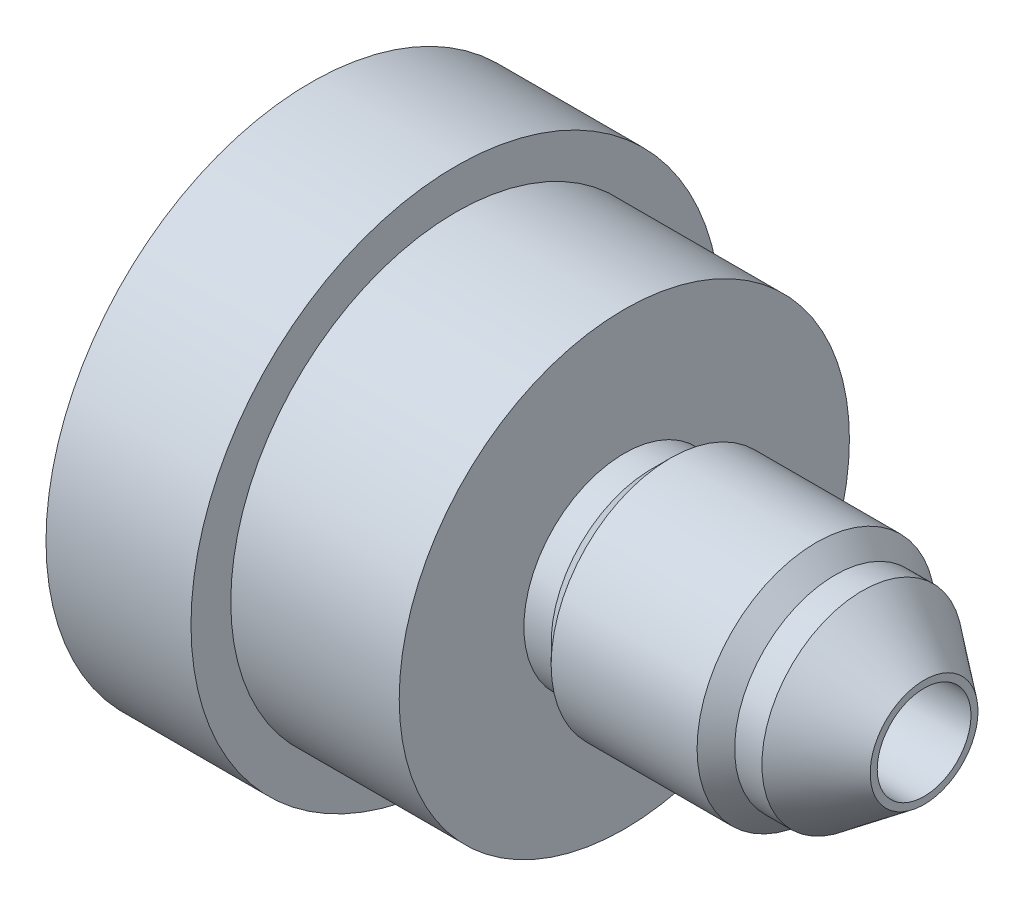
SolidWorks part; units mm, degrees
ref_plane "Front Plane" through (0, 0, 0) normal (0, 0, 1) x (1, 0, 0)
ref_plane "Top Plane" through (0, 0, 0) normal (0, 1, 0) x (1, 0, 0)
ref_plane "Right Plane" through (0, 0, 0) normal (1, 0, 0) x (0, 0, -1)
sketch "Sketch1" plane through (0, 0, 0) normal (0, 0, 1) x (1, 0, 0)
  line L0 (-14.2875, 0) -> (14.2875, 0) construction
  line L1 (-14.2875, 12.3444) -> (-14.2875, 11.176)
  line L2 (-14.2875, 11.176) -> (-2.3552, 2.1844)
  line L3 (-2.3552, 2.1844) -> (14.2875, 2.1844)
  line L4 (14.2875, 2.1844) -> (14.2875, 2.5121)
  line L5 (14.2875, 2.5121) -> (10.2477, 5.5562) construction
  line L6 (10.2477, 5.5562) -> (0.3175, 5.5562)
  line L7 (0.3175, 10.4902) -> (0.3175, 5.5562)
  line L8 (0.3175, 10.4902) -> (-7.5311, 10.4902)
  line L9 (-14.2875, 12.3444) -> (-7.5311, 12.3444)
  line L10 (-7.5311, 12.3444) -> (-7.5311, 10.4902)
  line L11 (10.2477, 5.5562) -> (14.2875, 5.5562)
  line L12 (14.2875, 5.5562) -> (14.2875, 2.5121)
  dimension "A" = 28.575
  dimension "OD" = 11.1125
  dimension "Min" = 4.3688
  dimension "D3" = 5.0241
  dimension "D4" = 37
  dimension "B" = 6.7564
  dimension "G" = 24.6888
  dimension "C" = 13.97
  dimension "F" = 20.9804
  dimension "D" = 22.352
revolve "Revolve1" add sketch "Sketch1" angle 360 about L0
ref_plane "Plane1" through (14.2875, 0, 0) normal (1, 0, 0) x (0, 0, -1)
sketch "Sketch2" plane through (14.2875, 0, 0) normal (1, 0, 0) x (0, 0, -1)
  circle A0 centre (0, 0) radius 5.5563
curve "Helix/Spiral1" pitch 1.27 height 13.97 radius 5.5563 centre (14.2875, 0, 0) axis (-1, 0, 0) start towards (0, 1, 0) parameters "Pitch"=1.27
sketch "Sketch4" plane through (0, 0, 0) normal (0, 0, 1) x (1, 0, 0)
  line L0 (14.2875, 5.5563) -> (15.3988, 5.5563)
  line L1 (14.2875, 5.5563) -> (14.7638, 4.7314)
  line L2 (14.7638, 4.7314) -> (14.9225, 4.7314)
  line L3 (14.9225, 4.7314) -> (15.3988, 5.5563)
  line L4 (14.8431, 4.7314) -> (14.8431, 5.5563) construction
  line L5 (14.5256, 5.1438) -> (15.1606, 5.1438) construction
  line L6 (14.2875, -5.5563) -> (14.2875, 5.5563) construction
  dimension "D1" = 60
  dimension "D2" = 0.1588
  dimension "D3" = 0.635
sweep "Cut-Sweep1" cut profiles "Sketch4" path "Helix/Spiral1" align with end faces yes
sketch "Sketch5" plane through (0, 0, 0) normal (0, 0, 1) x (1, 0, 0)
  line L0 (14.2875, 2.5121) -> (11.4098, 4.6806)
  line L1 (11.4098, 4.6806) -> (10.1398, 4.6806)
  line L2 (10.1398, 4.6806) -> (9.2641, 5.5562)
  line L3 (9.2641, 5.5562) -> (14.2875, 5.5562)
  line L4 (14.2875, 5.5562) -> (14.2875, 2.5121)
  line L5 (14.2875, 2.5121) -> (10.2477, 5.5562) construction
  line L6 (10.2477, 5.5562) -> (0.3175, 5.5562) construction
  line L7 (0.3175, 5.5563) -> (0.3175, 4.6806)
  line L8 (0.3175, 4.6806) -> (1.5875, 4.6806)
  line L9 (1.5875, 4.6806) -> (2.4632, 5.5562)
  line L10 (0.3175, 5.5563) -> (2.4632, 5.5562)
  line L11 (0, 0) -> (-14.2875, 0) construction
  line L12 (8.5523, 5.5562) -> (8.5523, -5.5562) construction
  line L13 (0, 0) -> (8.5523, 0) construction
  point P21 (8.5523, -5.5562)
  dimension "D1" = 45
  dimension "D2" = 0.0508
  dimension "D4" = 45
  dimension "D5" = 1.5875
revolve "Cut-Revolve1" cut sketch "Sketch5" angle 360 about L11
sketch "Sketch6" plane through (0, 0, 0) normal (0, 0, 1) x (1, 0, 0)
  line L0 (2.4632, 5.5562) -> (1.5875, 4.6806)
  line L1 (1.5875, 4.6806) -> (10.1398, 4.6806)
  line L2 (10.1398, 4.6806) -> (9.2641, 5.5562)
  line L3 (9.2641, 5.5562) -> (2.4632, 5.5562)
revolve "Revolve2" add sketch "Sketch6" angle 360 about L13
other "CPoint1" parameters "Diameter"=6.35, "StubLength"=25.4
ref_axis "Axis1" through (24.2875, 0, 0) along (-1, 0, 0)
equation "\"D3@Sketch1\" = \"Min@Sketch1\"*1.15"
equation "\"D3@Helix/Spiral1\" = \"C@Sketch1\""
equation "\"D2@Sketch4\" = \"Pitch@Helix/Spiral1\"*.125"
equation "\"D3@Sketch4\" = \"Pitch@Helix/Spiral1\"*.50"
equation "\"D3@Sketch5\" = \"Pitch@Helix/Spiral1\"*1."
equation "\"D5@Sketch5\" = \"Pitch@Helix/Spiral1\"*1.25"
